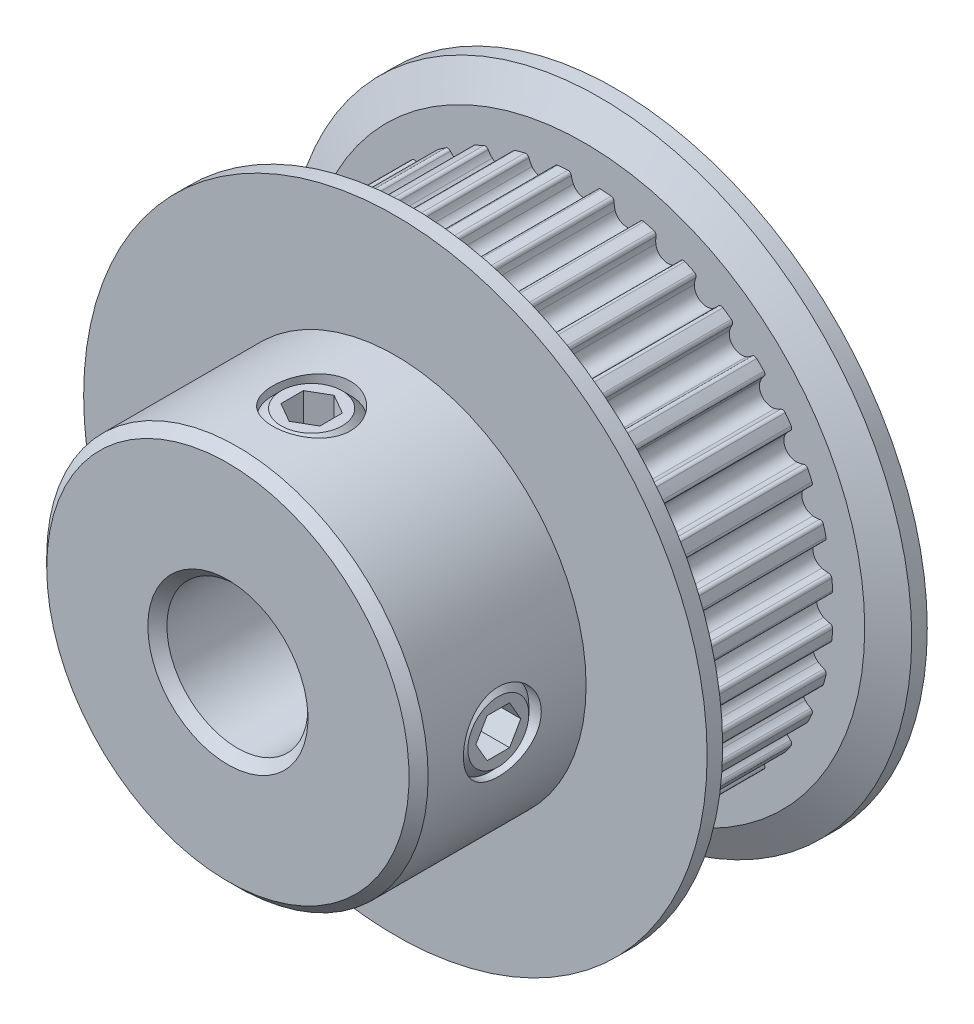
SolidWorks part; units mm, degrees
ref_plane "Front Plane" through (0, 0, 0) normal (0, 0, 1) x (1, 0, 0)
ref_plane "Top Plane" through (0, 0, 0) normal (0, 1, 0) x (1, 0, 0)
ref_plane "Right Plane" through (0, 0, 0) normal (1, 0, 0) x (0, 0, -1)
sketch "Sketch1" plane through (0, 0, 0) normal (0, 0, 1) x (1, 0, 0)
  line L1 (-1.8459, 10.4515) -> (1.8459, 10.4515) construction
  line L4 (0, 0) -> (0, 10.4515) construction
  line L5 (0, 10.4515) -> (0, 14.6065) construction
  line L6 (0, 11.4555) -> (1.9924, 11.2809) construction
  line L7 (1.9924, 11.2809) -> (2.8218, 11.1344) construction
  line L8 (1.9924, 11.2809) -> (1.8459, 10.4515) construction
  line L9 (-1.9924, 11.2809) -> (-1.8459, 10.4515) construction
  line L10 (-1.9482, 11.0308) -> (-2.4785, 14.0335)
  line L11 (-2.4785, 14.0335) -> (2.4785, 14.0335)
  line L12 (2.4785, 14.0335) -> (1.9482, 11.0308)
  circle A0 centre (0, 0) radius 11.4555 construction
  circle A1 centre (0, 0) radius 14.0335 construction
  circle A2 centre (0, 0) radius 11.2015 construction
  arc A3 (-0.4989, 10.7633) -> (0.4989, 10.7633) centre (0, 11.0065) ccw
  arc A4 (-0.4989, 10.7633) -> (-0.5884, 11.0497) centre (0.4, 11.2015) cw
  arc A5 (-1.9482, 11.0308) -> (-0.7467, 11.1766) centre (0, 0) cw
  arc A6 (-0.5884, 11.0497) -> (-0.7467, 11.1766) centre (-0.7367, 11.0269) ccw
  arc A7 (1.9482, 11.0308) -> (0.7467, 11.1766) centre (0, 0) ccw
  arc A8 (0.5884, 11.0497) -> (0.7467, 11.1766) centre (0.7367, 11.0269) cw
  arc A9 (0.4989, 10.7633) -> (0.5884, 11.0497) centre (-0.4, 11.2015) ccw
  point P6 (0, 20.9083)
  point P11 (0, 11.4555)
  point P13 (0, 14.0335)
  point P14 (0, 11.2015)
  dimension "D1" = 6.3018
  dimension "D2" = 3.151
sketch "Sketch2" plane through (0, 0, 0) normal (1, 0, 0) x (0, 0, -1)
  line L0 (-8.7249, 3.175) -> (8.7249, 3.175)
  line L1 (-8.7249, 3.175) -> (-8.7249, 8.585)
  line L2 (-8.7249, 8.585) -> (-1.1851, 8.585)
  line L3 (-1.1851, 8.585) -> (-1.1851, 14.0335)
  line L4 (-1.1851, 14.0335) -> (0.2149, 14.0335) construction
  line L5 (0.2149, 14.0335) -> (0.2149, 11.2015) construction
  line L6 (0.2149, 11.2015) -> (7.3249, 11.2015)
  line L7 (7.3249, 11.2015) -> (7.3249, 14.0335) construction
  line L8 (7.3249, 14.0335) -> (8.7249, 14.0335) construction
  line L9 (8.7249, 14.0335) -> (8.7249, 3.175)
  line L10 (-8.7249, 0) -> (8.7249, 0) construction
  line L11 (8.0249, 14.0335) -> (7.3249, 12.6175)
  line L12 (0.2149, 12.6175) -> (-0.4851, 14.0335)
  line L13 (-1.1851, 14.0335) -> (-0.4851, 14.0335)
  line L14 (0.2149, 12.6175) -> (0.2149, 11.2015)
  line L15 (7.3249, 11.2015) -> (7.3249, 12.6175)
  line L16 (8.0249, 14.0335) -> (8.7249, 14.0335)
  arc A0 (0.2149, 12.6175) -> (-0.4851, 14.0335) centre (-1.5673, 12.6175) ccw construction
  arc A1 (7.3249, 12.6175) -> (8.0249, 14.0335) centre (9.1071, 12.6175) cw construction
  point P12 (0.2149, 12.6175)
  point P14 (-0.4851, 14.0335)
  point P20 (7.3249, 12.6175)
  point P21 (8.0249, 14.0335)
  point P25 (7.3249, 0)
  point P26 (0.2149, 0)
revolve "Revolve1" add sketch "Sketch2" angle 360 mid plane about L10
sketch "Sketch3" plane through (0, 0, 0) normal (0, 0, 1) x (1, 0, 0)
  line L6 (2.4785, 14.0335) -> (-2.4785, 14.0335)
  line L7 (1.9482, 11.0308) -> (2.4785, 14.0335)
  line L8 (-2.4785, 14.0335) -> (-1.9482, 11.0308)
  line L9 (2.4785, 14.0335) -> (-2.4785, 14.0335)
  line L10 (1.9482, 11.0308) -> (2.4785, 14.0335)
  line L11 (-2.4785, 14.0335) -> (-1.9482, 11.0308)
  arc A8 (1.9482, 11.0308) -> (0.7467, 11.1766) centre (0, 0) ccw
  arc A9 (0.7467, 11.1766) -> (0.5884, 11.0497) centre (0.7367, 11.0269) ccw
  arc A10 (0.4989, 10.7633) -> (0.5884, 11.0497) centre (-0.4, 11.2015) ccw
  arc A11 (-0.4989, 10.7633) -> (0.4989, 10.7633) centre (0, 11.0065) ccw
  arc A12 (-0.5884, 11.0497) -> (-0.4989, 10.7633) centre (0.4, 11.2015) ccw
  arc A13 (-0.5884, 11.0497) -> (-0.7467, 11.1766) centre (-0.7367, 11.0269) ccw
  arc A14 (-0.7467, 11.1766) -> (-1.9482, 11.0308) centre (0, 0) ccw
  arc A15 (1.9482, 11.0308) -> (0.7467, 11.1766) centre (0, 0) ccw
  arc A16 (0.7467, 11.1766) -> (0.5884, 11.0497) centre (0.7367, 11.0269) ccw
  arc A17 (0.4989, 10.7633) -> (0.5884, 11.0497) centre (-0.4, 11.2015) ccw
  arc A18 (-0.4989, 10.7633) -> (0.4989, 10.7633) centre (0, 11.0065) ccw
  arc A19 (-0.5884, 11.0497) -> (-0.4989, 10.7633) centre (0.4, 11.2015) ccw
  arc A20 (-0.5884, 11.0497) -> (-0.7467, 11.1766) centre (-0.7367, 11.0269) ccw
  arc A21 (-0.7467, 11.1766) -> (-1.9482, 11.0308) centre (0, 0) ccw
  dimension "D1" = 0
extrude "Cut-Extrude1" cut sketch "Sketch3" against normal up to vertex (7.3249 mm away) from vertex up to point (0, 11.2015, -7.3249) starting at point (0, 11.2015, -0.2149)
pattern_circular "CirPattern1" count 36 over 360 about axis through (0, 0, 8.7249) along (0, 0, 1) of "Cut-Extrude1"
sketch "Sketch4" plane through (0, 0, 0) normal (1, 0, 0) x (0, -1, 0)
  line L0 (0, -1.1851) -> (0, -8.7249) construction
  line L1 (-8.585, -1.1851) -> (8.585, -1.1851) construction
  line L2 (-8.585, -8.7249) -> (8.585, -8.7249) construction
  circle A0 centre (0, -4.955) radius 1.7526
extrude "Cut-Extrude2" cut sketch "Sketch4" along normal through all
ref_plane "Plane1" through (0, 0, 4.955) normal (0, 0, 1) x (1, 0, 0)
sketch "Sketch5" plane through (0, 0, 4.955) normal (0, 0, 1) x (1, 0, 0)
  line L0 (0, 0.1664) -> (0, 8.585) construction
  line L1 (3.175, -1.3716) -> (3.175, 0)
  line L2 (3.556, -1.7526) -> (8.0232, -1.7526)
  line L3 (3.175, 0) -> (8.585, 0) construction
  line L4 (3.175, 0) -> (8.4042, 0)
  line L5 (8.4042, 0) -> (8.4042, -1.3716)
  line L6 (3.556, -1.7526) -> (3.175, -1.3716)
  line L7 (8.4042, -1.3716) -> (8.0232, -1.7526)
  circle A0 centre (0, 0) radius 8.585 construction
  circle A1 centre (0, 0) radius 3.175 construction
  point P2 (3.175, -1.7526)
  point P11 (8.4042, -1.7526)
revolve "Revolve2" add sketch "Sketch5" angle 360 mid plane about L4
sketch "Sketch6" plane through (8.4042, 5.3841, 0) normal (-1, 0, 0) x (0, -1, 0)
  line L1 (5.3841, 5.9669) -> (4.5078, 5.4609)
  line L2 (4.5078, 5.4609) -> (4.5078, 4.4491)
  line L3 (4.5078, 4.4491) -> (5.3841, 3.9431)
  line L4 (5.3841, 3.9431) -> (6.2604, 4.4491)
  line L5 (6.2604, 4.4491) -> (6.2604, 5.4609)
  line L6 (6.2604, 5.4609) -> (5.3841, 5.9669)
  circle A0 centre (5.3841, 4.955) radius 0.8763 construction
  dimension "D1" = 1.7526
extrude "Cut-Extrude3" cut sketch "Sketch6" along normal blind 1.3144
pattern_circular "CirPattern2" count 2 over 90 about axis through (0, 0, 8.7249) along (0, 0, 1) of "Cut-Extrude2", "Revolve2", "Cut-Extrude3"
chamfer "Chamfer1" distance 0.4293 angle 45 2 edges at (3.175, 0, 8.7249) (8.585, 0, 8.7249)
ref_axis "Center Axis 1" through (0, 0, -8.7249) along (0, 0, 1)
ref_plane "Contact Plane 1" through (0, 0, 8.7249) normal (0, 0, 1) x (1, 0, 0)
ref_plane "Contact Plane 2" through (0, 0, -8.7249) normal (0, 0, -1) x (-1, 0, 0)
equation "\"D2@Sketch1\" = \"D1@Sketch1\"/2"
equation "\"D1@Sketch6\" = \"Set Screw@Sketch4\" / 2"
equation "\"D1@Cut-Extrude3\" = \"D1@Sketch6\"*.75"
equation "\"D1@Chamfer1\"=\"Hub Dia@Sketch2\"*.025"
